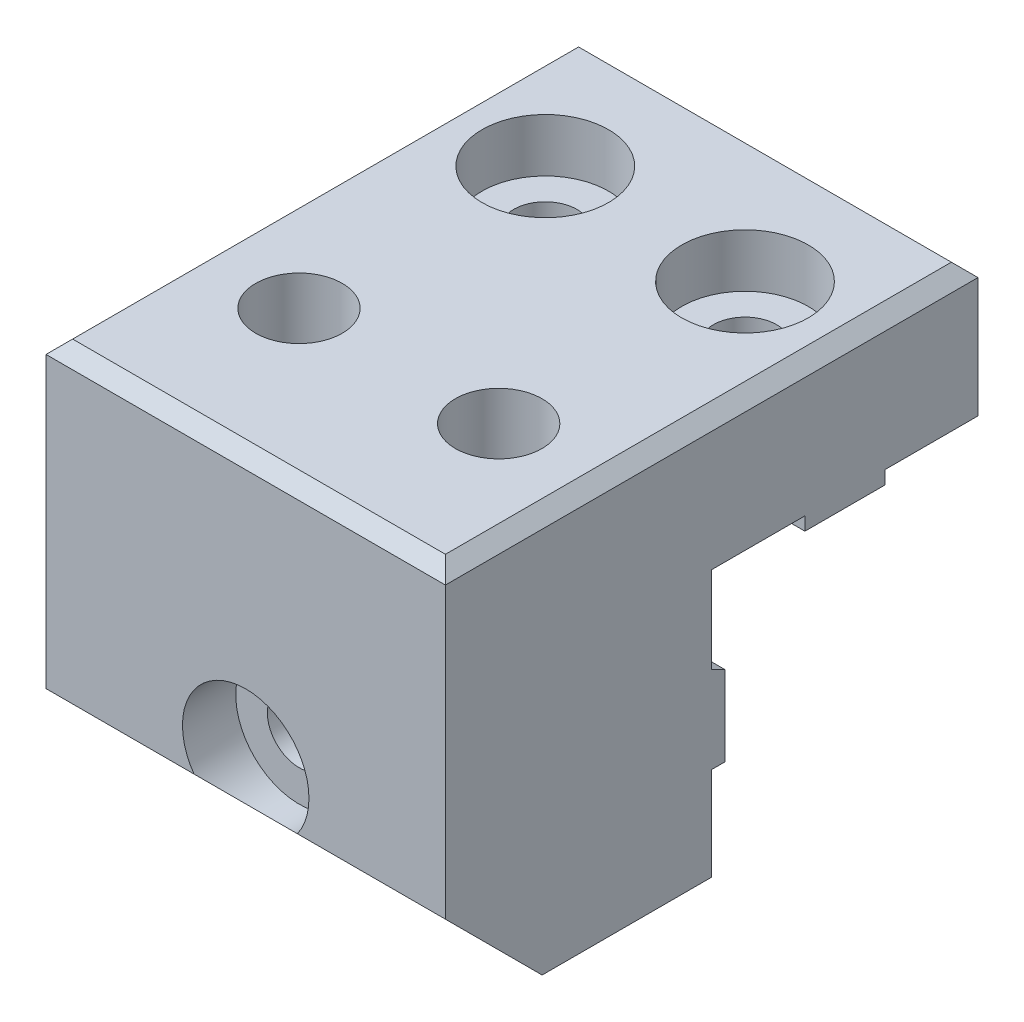
SolidWorks part; units mm, degrees
ref_plane "Plano frontal" through (0, 0, 0) normal (0, 0, 1) x (1, 0, 0)
ref_plane "Plano superior" through (0, 0, 0) normal (0, 1, 0) x (1, 0, 0)
ref_plane "Plano direito" through (0, 0, 0) normal (1, 0, 0) x (0, 0, -1)
sketch "Esboço1" plane through (0, 0, 0) normal (1, 0, 0) x (0, 0, -1)
  line L0 (21.2432, 12.7553) -> (-18.7568, 12.7553)
  line L1 (-18.7568, 12.7553) -> (-18.7568, -9.9813)
  line L2 (-18.7568, -9.9813) -> (-11.4935, -17.2447)
  line L3 (-11.4935, -17.2447) -> (1.2432, -17.2447)
  line L4 (1.2432, 2.7553) -> (21.2432, 2.7553)
  line L6 (1.2432, -17.2447) -> (1.2432, 2.7553)
  line L8 (21.2432, 2.7553) -> (21.2432, 12.7553)
  dimension "D1" = 20
  dimension "D2" = 12.7367
  dimension "D3" = 20
  dimension "D4" = 10
  dimension "D5" = 45
  dimension "D6" = 20
extrude "Ressalto-extrusão1" add sketch "Esboço1" along normal blind 30 contours L8 L0 L1 L2 L3 L6 region at (0, 0.7695, 3.3279)
sketch "Esboço2" plane through (0, 12.7553, 0) normal (0, 1, 0) x (1, 0, 0)
  line L0 (30, 21.2432) -> (0, 21.2432) construction
  line L1 (0, 1.2432) -> (30, 1.2432)
  line L2 (30, 21.2432) -> (0, 21.2432) construction
  line L3 (30, -18.7568) -> (0, -18.7568) construction
  line L4 (0, 21.2432) -> (0, -18.7568) construction
  line L5 (30, 21.2432) -> (30, -18.7568) construction
  circle A0 centre (7.5, 11.2432) radius 2.375
  circle A1 centre (22.5, 11.2432) radius 2.375
  circle A2 centre (7.5, -7.2568) radius 3.25
  circle A3 centre (22.5, -7.2568) radius 3.25
  circle A4 centre (7.5, 11.2432) radius 4.75
  circle A5 centre (22.5, 11.2432) radius 4.75
  dimension "D1" = 4.75
  dimension "D2" = 4.75
  dimension "D7" = 6.5
  dimension "D8" = 6.5
  dimension "D12" = 9.5
  dimension "D13" = 9.5
  dimension "D3" = 10
  dimension "D4" = 10
  dimension "D9" = 15
  dimension "D11" = 11.5
  dimension "D10" = 7.5
  dimension "D5" = 7.5
  dimension "D6" = 7.5
  dimension "D14" = 20
extrude "Corte-extrusão1" cut sketch "Esboço2" against normal up to next contours A0 | A1 | A3 | A2 region at (7.5, 12.7553, -11.2432) region at (22.5, 12.7553, -11.2432) region at (7.5, 12.7553, 7.2568) region at (22.5, 12.7553, 7.2568)
extrude "Corte-extrusão3" cut sketch "Esboço2<3>" against normal blind 4 contours A4 A0 | A5 A1 region at (2.8844, 12.7553, -11.2432) region at (17.8844, 12.7553, -11.2432)
sketch "Esboço2<3>" plane through (0, 12.7553, 0) normal (0, 1, 0) x (1, 0, 0) same geometry as "Esboço2"
sketch "Esboço3" plane through (0, 0, 18.7568) normal (0, 0, 1) x (1, 0, 0)
  line L0 (30, -17.2447) -> (0, -17.2447) construction
  line L1 (0, 12.7553) -> (0, -9.9813) construction
  circle A0 centre (15, -7.2447) radius 2.375
  circle A1 centre (15, -7.2447) radius 4.75
  line M2 (0, -9.9813) -> (30, -9.9813)
  dimension "D1" = 4.75
  dimension "D4" = 9.5
  dimension "D2" = 10
  dimension "D3" = 15
extrude "Corte-extrusão2" cut sketch "Esboço3" against normal up to next contours A0 region at (15, -7.2447, 18.7568)
extrude "Corte-extrusão4" cut sketch "Esboço3<3>" against normal blind 4 contours A1 M2 | A1 A0 M2 region at (19.4126, -8.6436, 18.7568) region at (15, -10.8034, 18.7568)
sketch "Esboço3<3>" plane through (0, 0, 18.7568) normal (0, 0, 1) x (1, 0, 0) same geometry as "Esboço3"
sketch "Esboço4" plane through (0, 2.7553, 0) normal (0, -1, 0) x (1, 0, 0)
  line L0 (7.5, -11.2432) -> (22.5, -11.2432) construction
  line L1 (0, -1.2432) -> (0, -21.2432) construction
  line L2 (12, -14.2432) -> (18, -14.2432)
  line L3 (12, -14.2432) -> (12, -8.2432)
  line L4 (12, -8.2432) -> (18, -8.2432)
  line L5 (18, -14.2432) -> (18, -8.2432)
  line L6 (12, -14.2432) -> (18, -8.2432) construction
  line L7 (12, -8.2432) -> (18, -14.2432) construction
  line L8 (0, -8.2432) -> (3, -8.2432)
  line L9 (0, -8.2432) -> (0, -14.2432)
  line L10 (0, -14.2432) -> (3, -14.2432)
  line L11 (3, -8.2432) -> (3, -14.2432)
  line L12 (30, -1.2432) -> (30, -21.2432) construction
  line L13 (30, -8.2432) -> (27, -8.2432)
  line L14 (30, -8.2432) -> (30, -14.2432)
  line L15 (30, -14.2432) -> (27, -14.2432)
  line L16 (27, -8.2432) -> (27, -14.2432)
  circle A0 centre (7.5, -11.2432) radius 2.375 construction
  point P4 (15, -11.2432)
  dimension "D1" = 6
  dimension "D2" = 4.5
  dimension "D3" = 4.5
  dimension "D4" = 4.5
extrude "Ressalto-extrusão2" add sketch "Esboço4" along normal blind 1
sketch "Esboço5" plane through (0, 2.7553, 0) normal (0, -1, 0) x (1, 0, 0)
  circle A2 centre (7.5, 7.2568) radius 6.5
  circle A3 centre (22.5, 7.2568) radius 6.5
  dimension "D1" = 13
  dimension "D2" = 13
extrude "Corte-extrusão5" cut sketch "Esboço5" along normal through all contours A2 | A3 region at (7.5, 2.7553, 7.2568) region at (22.5, 2.7553, 7.2568)
chamfer "Chanfro1" distance 1 angle 45 4 edges at (15, 12.7553, -21.2432) (30, 12.7553, -1.2432) (15, 12.7553, 18.7568) (0, 12.7553, -1.2432)
sketch "Esboço6" plane through (0, 0, -1.2432) normal (0, 0, -1) x (-1, 0, 0)
  line L0 (-32.4547, -7.2447) -> (1.8245, -7.2447) construction
  line L1 (-30, -17.2447) -> (-30, 2.7553) construction
  line L2 (-30, -4.2447) -> (-20, -4.2447)
  line L3 (-30, -4.2447) -> (-30, -10.2447)
  line L4 (-30, -10.2447) -> (-20, -10.2447)
  line L5 (-20, -4.2447) -> (-20, -10.2447)
  line L6 (-10, -4.2447) -> (0, -4.2447)
  line L7 (-10, -4.2447) -> (-10, -10.2447)
  line L8 (-10, -10.2447) -> (0, -10.2447)
  line L9 (0, -4.2447) -> (0, -10.2447)
  line L10 (0, -17.2447) -> (0, 2.7553) construction
  point P2 (-15, -7.2447)
  dimension "D1" = 6
  dimension "D2" = 3
  dimension "D3" = 5
  dimension "D4" = 5
extrude "Ressalto-extrusão3" add sketch "Esboço6" along normal blind 1
chamfer "Chanfro2" distance 0.5 distance2 1 2 edges at (25, -4.2447, -1.2432) (5, -4.2447, -1.2432) first distance on face at (17.375, -7.2447, -1.2432)
equation "\"D4@Esboço2\"=\"D3@Esboço2\""
equation "\"D8@Esboço2\"=\"D7@Esboço2\""
equation "\"D5@Esboço2\"=\"D10@Esboço2\""
equation "\"D6@Esboço2\"=\"D10@Esboço2\""
equation "\"D2@Esboço2\"=\"D1@Esboço2\""
equation "\"D13@Esboço2\"=\"D12@Esboço2\""
equation "\"D3@Esboço4\"=\"D2@Esboço4\""
equation "\"D4@Esboço4\"=\"D2@Esboço4\""
equation "\"D2@Esboço5\"=\"D1@Esboço5\""
